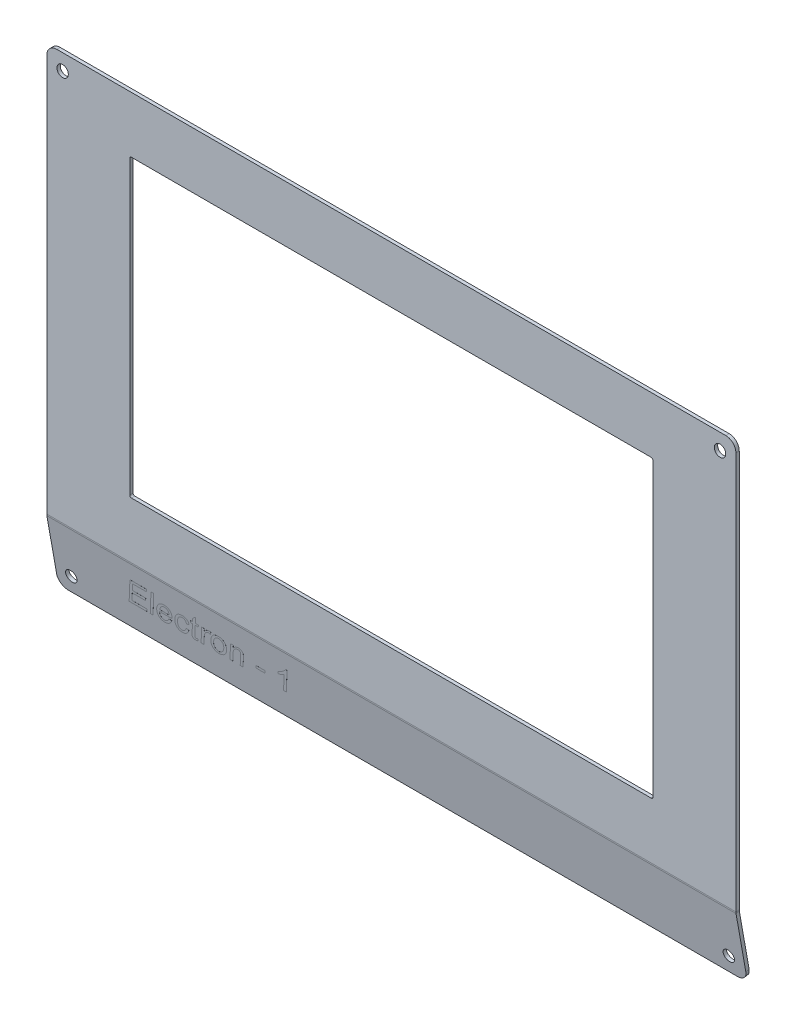
SolidWorks part; units mm, degrees
note: The reader was unsure of these and kept them because the rebuilt part matched: flange length of "Ребро-кромка1".
ref_plane "Спереди" through (0, 0, 0) normal (0, 0, 1) x (1, 0, 0)
ref_plane "Сверху" through (0, 0, 0) normal (0, 1, 0) x (1, 0, 0)
ref_plane "Справа" through (0, 0, 0) normal (1, 0, 0) x (0, 0, -1)
sketch "Эскиз2" plane through (0, 0, 0) normal (0, 0, 1) x (1, 0, 0)
  line L1 (102.75, 60.75) -> (-102.75, 60.75)
  line L2 (102.75, 60.75) -> (102.75, -60.75)
  line L3 (102.75, -60.75) -> (-102.75, -60.75)
  line L4 (-102.75, 60.75) -> (-102.75, -60.75)
  line L5 (102.75, 60.75) -> (-102.75, -60.75) construction
  line L6 (102.75, -60.75) -> (-102.75, 60.75) construction
  point P0 (0, 0)
  dimension "D1" = 205.5
  dimension "D2" = 121.5
base flange "Базовая кромка1" sketch "Эскиз2" thickness 1 reverse thickness direction no parameters "D1"=1.6
edge flange "Ребро-кромка1" sketch "Эскиз11" flange angle 170 flange length 20 flange position bend outside bend radius 1.6 thickness 1 relief rectangular parameters "D6"=10
sketch "Эскиз11" plane through (0, -60.75, -1) normal (0, -0.1736, 0.9848) x (-1, 0, 0)
  line L0 (102.75, 0) -> (-102.75, 0) construction
  line L1 (102.75, 0) -> (-102.75, 0)
  line L2 (-102.75, 0) -> (-102.75, 19.9125)
  line L3 (-102.75, 19.9125) -> (102.75, 19.9125)
  line L4 (102.75, 19.9125) -> (102.75, 0)
bend "EdgeBend1" bend radius 1.6 bend angle 10 parameters "D5"=1
fillet "Скругление1" radius 3 4 edges at (102.75, -80.5868, -3.9654) (-102.75, -80.5868, -3.9654) (-102.75, 60.75, -0.5) (102.75, 60.75, -0.5)
sketch "Эскиз12" plane through (0, 0, 0) normal (0, 0, 1) x (1, 0, 0)
  line L1 (78, -44) -> (-78, -44)
  line L2 (78, -44) -> (78, 44)
  line L3 (78, 44) -> (-78, 44)
  line L4 (-78, -44) -> (-78, 44)
  line L5 (78, -44) -> (-78, 44) construction
  line L6 (78, 44) -> (-78, -44) construction
  point P0 (0, 0)
  dimension "D1" = 156
  dimension "D2" = 88
extrude "Вырез-Вытянуть2" cut sketch "Эскиз12" against normal blind 10 normal cut yes
fillet "Скругление2" radius 0.5 4 edges at (78, -44, -0.5) (78, 44, -0.5) (-78, 44, -0.5) (-78, -44, -0.5)
hole_wizard "Сверло под метчик  спиральное M31" positions "Трехмерный эскиз3" profile "Эскиз15" hole size "M3" standard "Ansi Metric"
sketch3d "Трехмерный эскиз3"
  circle A0 centre (-98.0213, -75.5969, -3.5932) radius 1.575 construction
  circle A1 centre (98.0213, -75.5969, -3.5932) radius 1.575 construction
  circle A2 centre (98.0213, 55.9949, -1.0022) radius 1.575 construction
  circle A3 centre (-98.0213, 55.9949, -1.0022) radius 1.575 construction
  point P3 (-98.0213, -75.7706, -2.6084)
  point P10 (-98.0213, -75.8704, -2.0422)
  point P17 (98.0213, -75.7706, -2.6084)
  point P26 (98.0213, -75.8704, -2.0422)
  point P27 (-98.0213, 55.9949, 0)
  point P29 (98.0213, 55.9949, 0)
  point P35 (98.0213, 55.9949, 0.5728)
  point P39 (-98.0213, 55.9949, 0.5728)
sketch "Эскиз15" plane through (-98.0213, -75.7706, -2.6084) normal (1, 0, 0) x (0, -0.9848, -0.1736)
  line L0 (0, 0) -> (0, 9.5215)
  line L1 (0, 9.5215) -> (1.7, 8.5)
  line L2 (1.7, 8.5) -> (1.7, 0)
  line L5 (1.7, 0) -> (0, 0)
  line L10 (0, 9.5215) -> (-1.7, 8.5) construction
  line L11 (0, -6.35) -> (0, 107.95) construction
  dimension "Диаметр отверстия" = 3.4
  dimension "Глубина отверстия" = 8.5
  dimension "Угол заточки сверла" = 118
sketch "Эскиз16" plane through (0, -1.8387, 10.4278) normal (0, -0.1736, 0.9848) x (1, 0, 0)
  text T0 "Electron - 1" height 7
  point P1 (-75.3575, -73.9313)
  point P2 (0, 0)
  point P3 (0, 0)
  point P4 (0, 0)
  point P5 (-78.1729, -73.4623)
  point P6 (0, 0)
  point P7 (-78.0902, -71.9749)
  point P8 (0, 0)
extrude "Бобышка-Вытянуть1" add sketch "Эскиз16" along normal blind 0.01
sketch "Сгиб-Линии1" plane through (0, 0, 0) normal (0, 1, 0) x (1, 0, 0)
sketch "Граничная рамка1" plane through (0, 0, 0) normal (0, 1, 0) x (1, 0, 0)
sheet metal parameters "Листовой металл6" thickness 1 parameters "D1"=1.6
flat pattern "Развертка6" [suppressed]
sketch "Сгиб-Линии2" plane through (0, 0, 0) normal (0, 1, 0) x (1, 0, 0)
sketch "Граничная рамка2" [suppressed] plane through (0, 0, 0) normal (0, 1, 0) x (1, 0, 0)
sheet metal parameters "Листовой металл7" thickness 1 parameters "D1"=1.6
flat pattern "Развертка6" [suppressed]
sketch "Сгиб-Линии2" plane through (0, 0, 0) normal (0, 1, 0) x (1, 0, 0)
sketch "Граничная рамка2" [suppressed] plane through (0, 0, 0) normal (0, 1, 0) x (1, 0, 0)
bend of the flat pattern "Плоское состояние-<EdgeBend1>1"
sheet metal parameters "Листовой металл8" thickness 1 parameters "D1"=1.6
flat pattern "Развертка6" [suppressed]
sketch "Сгиб-Линии2" plane through (0, 0, 0) normal (0, 1, 0) x (1, 0, 0)
sketch "Граничная рамка2" [suppressed] plane through (0, 0, 0) normal (0, 1, 0) x (1, 0, 0)
bend of the flat pattern "Плоское состояние-<EdgeBend1>1"
sheet metal parameters "Листовой металл9" thickness 1 parameters "D1"=1.6
flat pattern "Развертка6" [suppressed]
sketch "Сгиб-Линии2" plane through (0, 0, 0) normal (0, 1, 0) x (1, 0, 0)
sketch "Граничная рамка2" [suppressed] plane through (0, 0, 0) normal (0, 1, 0) x (1, 0, 0)
bend of the flat pattern "Плоское состояние-<EdgeBend1>1"
sheet metal parameters "Листовой металл10" thickness 1 parameters "D1"=1.6
flat pattern "Развертка6" [suppressed]
sketch "Сгиб-Линии2" plane through (0, 0, 0) normal (0, 1, 0) x (1, 0, 0)
sketch "Граничная рамка2" [suppressed] plane through (0, 0, 0) normal (0, 1, 0) x (1, 0, 0)
bend of the flat pattern "Плоское состояние-<EdgeBend1>1"
